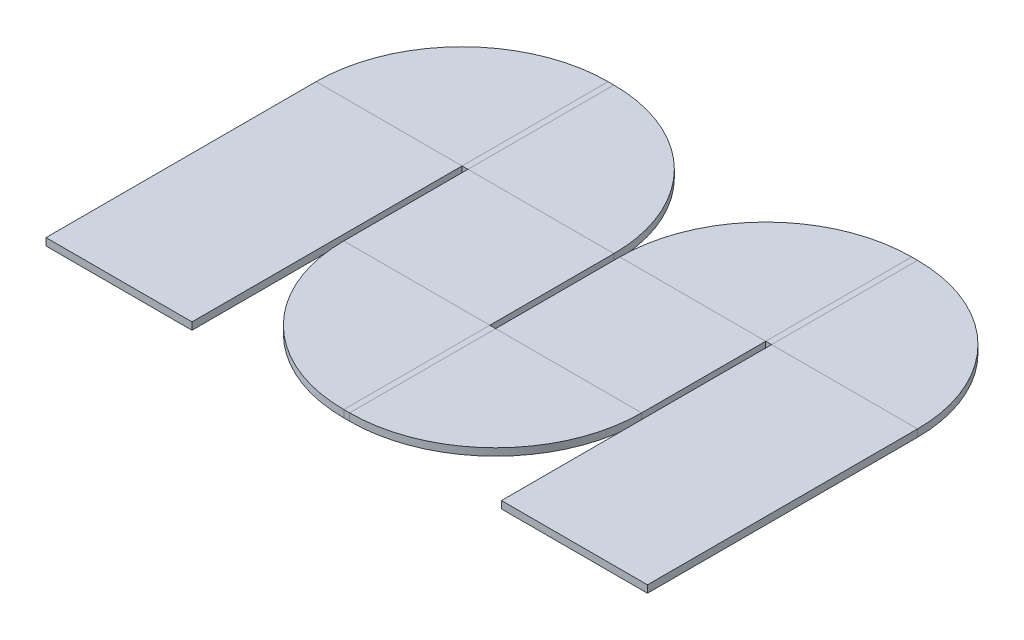
SolidWorks part; units mm, degrees
ref_plane "Front Plane" through (0, 0, 0) normal (0, 0, 1) x (1, 0, 0)
ref_plane "Top Plane" through (0, 0, 0) normal (0, 1, 0) x (1, 0, 0)
ref_plane "Right Plane" through (0, 0, 0) normal (1, 0, 0) x (0, 0, -1)
sketch "Sketch6" plane through (0, 0, 0) normal (0, 0, 1) x (1, 0, 0)
  line L1 (31.75, -15.875) -> (-31.75, -15.875)
  line L2 (31.75, -15.875) -> (31.75, -19.05)
  line L3 (31.75, -19.05) -> (-31.75, -19.05)
  line L4 (-31.75, -15.875) -> (-31.75, -19.05)
  line L5 (31.75, -15.875) -> (-31.75, -19.05) construction
  line L6 (31.75, -19.05) -> (-31.75, -15.875) construction
  point P0 (0, -17.4625)
  dimension "D1" = 63.5
  dimension "D2" = 3.175
  dimension "D3" = 19.05
sketch "Sketch1" plane through (0, 0, 0) normal (0, 1, 0) x (1, 0, 0)
  line L0 (0, 0) -> (0, 117.475)
  line L1 (31.75, 149.225) -> (34.29, 149.225)
  line L2 (66.04, 117.475) -> (66.04, 63.5)
  line L3 (97.79, 31.75) -> (100.33, 31.75)
  line L4 (132.08, 63.5) -> (132.08, 117.475)
  line L5 (163.83, 149.225) -> (166.37, 149.225)
  line L6 (198.12, 117.475) -> (198.12, 0)
  arc A0 (97.79, 31.75) -> (66.04, 63.5) centre (97.79, 63.5) cw
  arc A1 (66.04, 117.475) -> (34.29, 149.225) centre (34.29, 117.475) ccw
  arc A2 (31.75, 149.225) -> (0, 117.475) centre (31.75, 117.475) ccw
  arc A3 (198.12, 117.475) -> (166.37, 149.225) centre (166.37, 117.475) ccw
  arc A4 (163.83, 149.225) -> (132.08, 117.475) centre (163.83, 117.475) ccw
  arc A5 (132.08, 63.5) -> (100.33, 31.75) centre (100.33, 63.5) cw
  point P12 (0, 149.225)
  dimension "D2" = 31.75
  dimension "D3" = 66.04
  dimension "D4" = 31.75
  dimension "D1" = 149.225
sweep "Sweep1" add profiles "Sketch6" path "Sketch1"
